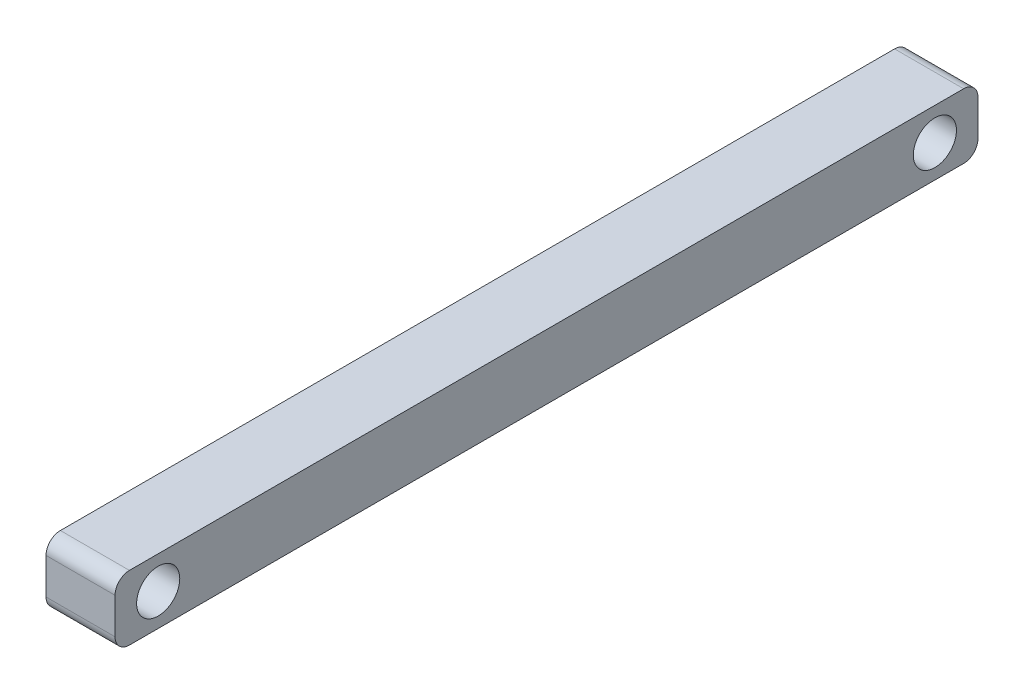
SolidWorks part; units mm, degrees
ref_plane "Alzado" through (0, 0, 0) normal (0, 0, 1) x (1, 0, 0)
ref_plane "Planta" through (0, 0, 0) normal (0, 1, 0) x (1, 0, 0)
ref_plane "Vista lateral" through (0, 0, 0) normal (1, 0, 0) x (0, 0, -1)
sketch "Croquis1" plane through (0, 0, 0) normal (1, 0, 0) x (0, 0, -1)
  line L0 (-29, 2.25) -> (29, 2.25)
  line L2 (-30, 0) -> (30, 0) construction
  line L3 (-30, 1.25) -> (-30, -1.25)
  line L4 (-29, -2.25) -> (29, -2.25)
  line L5 (30, 1.25) -> (30, -1.25)
  arc A0 (-30, -1.25) -> (-29, -2.25) centre (-29, -1.25) ccw
  arc A1 (-30, 1.25) -> (-29, 2.25) centre (-29, 1.25) cw
  arc A2 (29, -2.25) -> (30, -1.25) centre (29, -1.25) ccw
  arc A3 (29, 2.25) -> (30, 1.25) centre (29, 1.25) cw
  point P1 (0, 0)
  point P9 (-30, -2.25)
  point P13 (-30, 2.25)
  point P16 (30, -2.25)
  point P19 (30, 2.25)
  dimension "D3" = 1
  dimension "D4" = 1
  dimension "D1" = 2.25
  dimension "D2" = 60
extrude "Saliente-Extruir1" add sketch "Croquis1" along normal mid plane 4.8
sketch "Croquis2" plane through (0, 0, 0) normal (1, 0, 0) x (0, 0, -1)
  line L0 (-30, 1.25) -> (-30, -1.25) construction
  line L1 (30, -1.25) -> (30, 1.25) construction
  circle A0 centre (-27, 0) radius 1.5
  circle A1 centre (27, 0) radius 1.5
  dimension "D1" = 3
  dimension "D3" = 3
  dimension "D2" = 3
  dimension "D4" = 3
extrude "Cortar-Extruir1" cut sketch "Croquis2" against normal through all both and the other way through all
